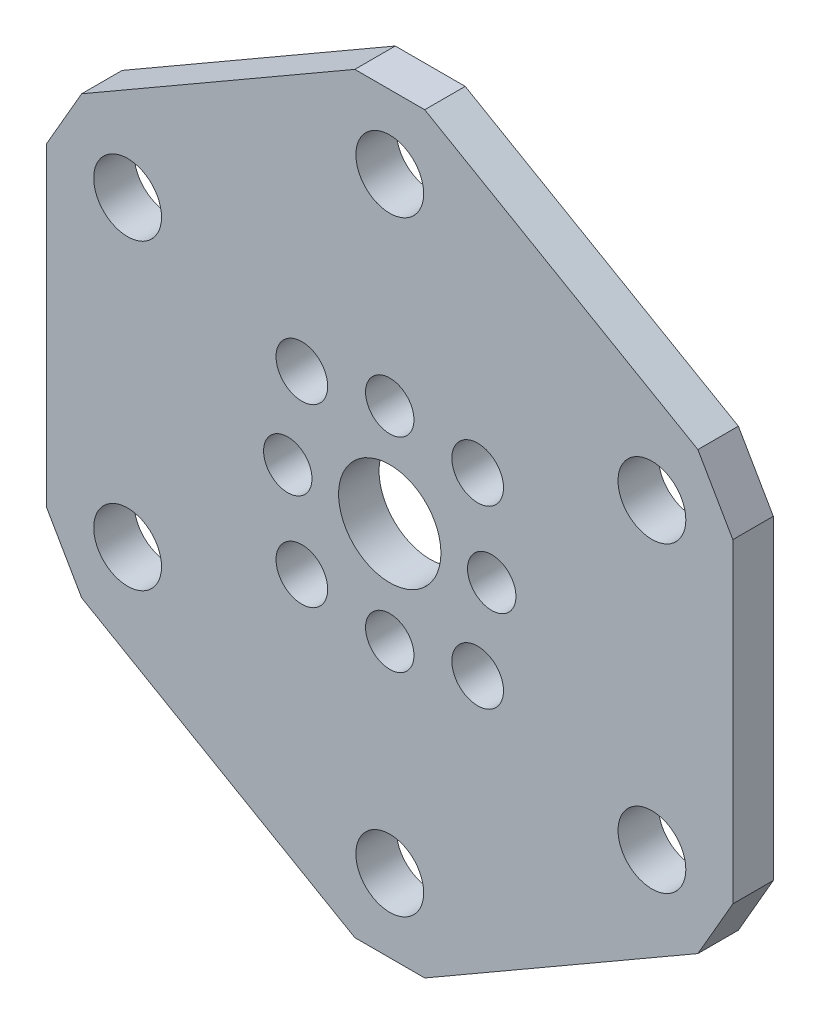
SolidWorks part; units mm, degrees
ref_plane "Front" through (0, 0, 0) normal (0, 0, 1) x (1, 0, 0)
ref_plane "Top" through (0, 0, 0) normal (0, 1, 0) x (1, 0, 0)
ref_plane "Right" through (0, 0, 0) normal (1, 0, 0) x (0, 0, -1)
ref_plane "Plane1" through (0, 0, 0) normal (0, 0, -1) x (-1, 0, 0)
sketch "Sketch1" plane through (0, 0, 0) normal (0, 0, -1) x (-1, 0, 0)
  line L0 (2.7424, 29.4974) -> (-2.7424, 29.4974)
  line L1 (-2.7424, 29.4974) -> (-24.1743, 17.1237)
  line L2 (-24.1743, 17.1237) -> (-26.9167, 12.3737)
  line L3 (-26.9167, 12.3737) -> (-26.9167, -12.3737)
  line L4 (-26.9167, -12.3737) -> (-24.1743, -17.1237)
  line L5 (-24.1743, -17.1237) -> (-2.7424, -29.4974)
  line L6 (-2.7424, -29.4974) -> (2.7424, -29.4974)
  line L7 (2.7424, -29.4974) -> (24.1743, -17.1237)
  line L8 (24.1743, -17.1237) -> (26.9167, -12.3737)
  line L9 (26.9167, -12.3737) -> (26.9167, 12.3737)
  line L10 (26.9167, 12.3737) -> (24.1743, 17.1237)
  line L11 (24.1743, 17.1237) -> (2.7424, 29.4974)
  line L12 (0, 0) -> (0, 23.75) construction
  line L13 (0, 0) -> (-8, 0) construction
  circle A0 centre (20.5681, 11.875) radius 2.66
  circle A1 centre (20.5681, -11.875) radius 2.66
  circle A2 centre (0, -23.75) radius 2.66
  circle A5 centre (0, 23.75) radius 2.66
  circle A6 centre (0, 0) radius 4.0144
  circle A9 centre (-20.5681, -11.875) radius 2.66
  circle A10 centre (-20.5681, 11.875) radius 2.66
  circle A11 centre (-6.8966, 6.8966) radius 2.0267
  circle A12 centre (-6.8966, -6.8966) radius 2.0267
  circle A13 centre (6.8966, -6.8966) radius 2.0267
  circle A14 centre (6.8966, 6.8966) radius 2.0267
  circle A15 centre (-8, 0) radius 1.8987
  circle A16 centre (0, 8) radius 1.8986
  circle A17 centre (8, 0) radius 1.8986
  circle A18 centre (0, -8) radius 1.8987
  point P45 (0, 0)
  point P46 (0, 0)
  dimension "D2" = 6
  dimension "D4" = 3.7973
  dimension "D5" = 4
  dimension "D1" = 23.75
  dimension "D3" = 8
extrude "Boss-Extrude1" add sketch "Sketch1" against normal blind 3.175
